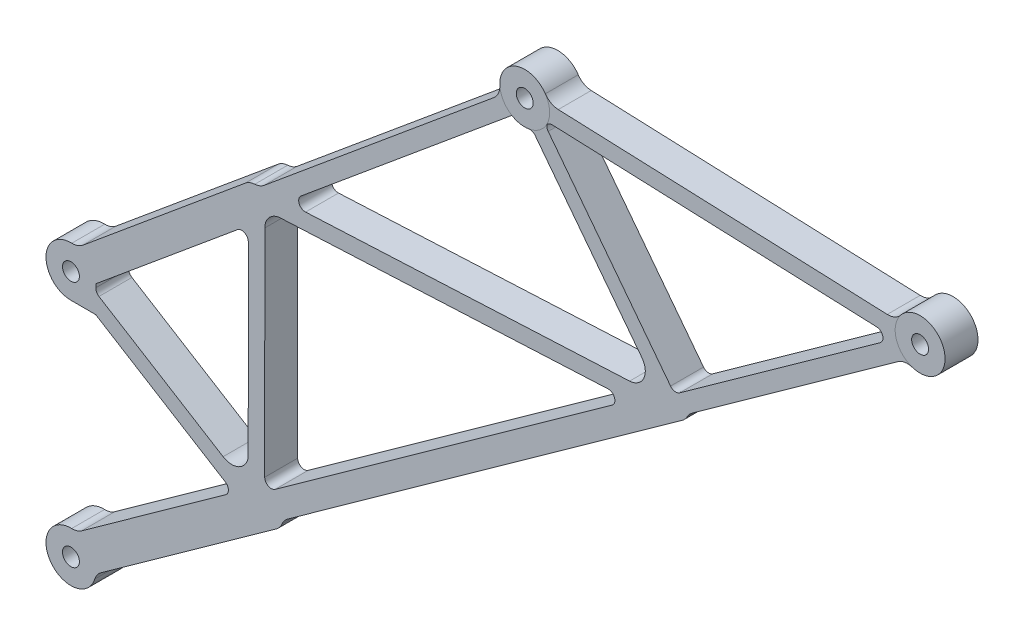
SolidWorks part; units mm, degrees
material "7075-T6 (SN)"
ref_plane "Front Plane" through (0, 0, 0) normal (0, 0, 1) x (1, 0, 0)
ref_plane "Top Plane" through (0, 0, 0) normal (0, 1, 0) x (1, 0, 0)
ref_plane "Right Plane" through (0, 0, 0) normal (1, 0, 0) x (0, 0, -1)
sketch "Sketch1" plane through (0, 0, 0) normal (0, 0, 1) x (1, 0, 0)
  line L0 (1800.568, -34.4734) -> (1473.2701, -269.0447) construction
  line L1 (1800.568, -34.4734) -> (1648.17, -28.4813) construction
  line L2 (1648.17, -28.4813) -> (1473.2701, -173.7947) construction
  line L3 (1547.9863, -115.8456) -> (1539.8135, -106.0088) construction
  line L4 (1473.2701, -269.0447) -> (1473.2701, -173.7947) construction
  line L7 (1806.1684, -42.2876) -> (1478.8705, -276.859)
  line L8 (1800.9457, -24.8669) -> (1648.5477, -18.8749)
  line L9 (1642.0262, -21.0867) -> (1467.1264, -166.4001)
  line L10 (1473.2701, -183.4086) -> (1482.7951, -183.4086)
  line L11 (1482.7951, -254.4058) -> (1482.7951, -183.4086) construction
  line L12 (1482.7951, -269.0447) -> (1482.7951, -173.7947) construction
  line L13 (1795.0417, -42.3402) -> (1709.5839, -103.5871)
  line L14 (1791.6252, -30.9443) -> (1657.3622, -25.6653)
  line L15 (1791.3758, -37.2894) -> (1657.1127, -32.0104)
  line L16 (1639.1612, -31.8383) -> (1543.9283, -110.9614)
  line L17 (1643.2192, -36.7225) -> (1541.6343, -121.1231)
  line L18 (1545.2991, -217.4222) -> (1541.6001, -212.2609) construction
  line L19 (1791.1982, -37.2824) -> (1705.8848, -98.4257)
  line L20 (1475.4382, -259.6785) -> (1536.0064, -216.2698)
  line L21 (1798.7185, -31.8927) -> (1471.4206, -266.4641) construction
  line L23 (1648.17, -28.4813) -> (1706.9348, -105.006) construction
  line L24 (1706.9348, -105.006) -> (1544.8124, -112.8199) construction
  line L25 (1544.8124, -112.8199) -> (1544.7729, -217.952) construction
  line L26 (1544.7729, -217.952) -> (1473.2701, -173.7947) construction
  line L29 (1651.1787, -37.6123) -> (1700.7207, -102.1268)
  line L30 (1656.2151, -33.7448) -> (1705.8848, -98.4257)
  line L31 (1650.6882, -26.5476) -> (1709.453, -103.0722) construction
  line L32 (1645.6518, -30.4151) -> (1704.4166, -106.9398) construction
  line L33 (1700.7207, -102.1268) -> (1556.1093, -109.0967)
  line L34 (1688.8733, -109.0552) -> (1547.9863, -115.8456)
  line L35 (1706.7819, -101.8347) -> (1544.6596, -109.6486) construction
  line L36 (1707.0876, -108.1773) -> (1544.9653, -115.9912) construction
  line L37 (1541.6343, -121.1231) -> (1541.6001, -212.2609)
  line L38 (1547.9863, -115.8456) -> (1547.9509, -210.053)
  line L39 (1541.6374, -112.8187) -> (1541.5979, -217.9508) construction
  line L40 (1547.9874, -112.8211) -> (1547.9479, -217.9531) construction
  line L41 (1541.6001, -212.2609) -> (1482.6593, -175.8614)
  line L42 (1536.0064, -216.2698) -> (1479.3227, -181.2642)
  line L43 (1543.1046, -220.6533) -> (1471.6019, -176.4961) construction
  line L44 (1546.4412, -215.2506) -> (1474.9384, -171.0933) construction
  line L47 (1554.2393, -218.8273) -> (1482.8363, -270.0011)
  line L48 (1650.199, -30.9234) -> (1475.2991, -176.2368) construction
  line L49 (1646.141, -26.0392) -> (1471.2411, -171.3526) construction
  line L50 (1800.4433, -37.6459) -> (1648.0453, -31.6539) construction
  line L51 (1800.6927, -31.3008) -> (1648.2947, -25.3088) construction
  line L54 (1802.4175, -37.054) -> (1475.1197, -271.6254) construction
  line L56 (1554.2393, -218.8273) -> (1553.1296, -217.2789)
  line L57 (1542.3863, -109.1054) -> (1475.7164, -164.4973)
  line L58 (1543.9283, -110.9614) -> (1542.3863, -109.1054)
  line L59 (1541.6331, -124.2612) -> (1482.8584, -173.0934)
  line L61 (1705.8848, -98.4257) -> (1713.3347, -108.8206) construction
  line L62 (1710.3237, -104.6193) -> (1553.1296, -217.2789)
  line L63 (1709.5839, -103.5871) -> (1710.3237, -104.6193)
  line L64 (1547.9509, -210.053) -> (1688.8733, -109.0552)
  circle A0 centre (1800.568, -34.4734) radius 3.2639 construction
  circle A1 centre (1648.17, -28.4813) radius 3.2639 construction
  circle A2 centre (1473.2701, -173.7947) radius 3.2639 construction
  circle A3 centre (1473.2701, -269.0447) radius 3.2639 construction
  circle A4 centre (1800.568, -34.4734) radius 3.2639
  circle A5 centre (1648.17, -28.4813) radius 3.2639
  circle A6 centre (1473.2701, -173.7947) radius 3.2639
  circle A7 centre (1473.2701, -269.0447) radius 3.2639
  circle A8 centre (1473.2701, -269.0447) radius 9.6139
  circle A9 centre (1473.2701, -173.7947) radius 9.6139
  circle A10 centre (1648.17, -28.4813) radius 9.6139
  circle A11 centre (1800.568, -34.4734) radius 9.6139
  dimension "D10" = 6.35
  dimension "D11" = 3.175
  dimension "D12" = 94.5014
  dimension "D26" = 6.35
  dimension "D27" = 5.588
  dimension "D28" = 5.588
  dimension "D29" = 4.445
  dimension "D30" = 4.445
  dimension "D13" = 114.3
  dimension "D1" = 6.35
  dimension "D3" = 9.525
  dimension "D4" = 3.175
  dimension "D5" = 3.175
  dimension "D6" = 3.175
  dimension "D7" = 3.175
  dimension "D8" = 3.175
  dimension "D9" = 3.175
  dimension "D15" = 3.175
  dimension "D16" = 3.175
  dimension "D17" = 3.175
  dimension "D18" = 3.175
  dimension "D19" = 3.175
  dimension "D22" = 3.175
  dimension "D23" = 3.175
extrude "Boss-Extrude1" add sketch "Sketch1" along normal mid plane 12.7 contours A8 A7 | A11 L15 L19 L30 A10 L29 L33 L17 L34 L64 L38 L37 L41 A9 L42 L20 A8 L47 L56 L62 L63 L13 | A9 A6 | A10 L16 L58 L57 A9 L59 L37 L17 | A10 A5 | A11 L14 A10 L15 | A11 A4 | L20 L42 region at (1800.6122, -43.8152, 0) region at (1464.1092, -270.8749, 0) region at (1749.9975, -69.7332, 0) region at (1724.369, -31.4773, 0) region at (1653.8712, -21.0807, 0) region at (1479.0973, -182.7389, 0) region at (1464.4838, -176.9685, 0) region at (1549.361, -110.5007, 0)
fillet "Fillet2" radius 6.35 10 edges at (1475.4382, -259.6785, 0) (1639.1612, -31.8383, 0) (1657.3622, -25.6653, 0) (1795.0417, -42.3402, 0) (1791.6252, -30.9443, 0) (1482.8363, -270.0011, 0) (1475.7164, -164.4973, 0) (1541.6001, -212.2609, 0) (1547.9863, -115.8456, 0) (1700.7207, -102.1268, 0)
fillet "Fillet3" radius 2.54 11 edges at (1791.1982, -37.2824, 0) (1482.6593, -175.8614, 0) (1536.0064, -216.2698, 0) (1556.1093, -109.0967, 0) (1705.8848, -98.4257, 0) (1651.1787, -37.6123, 0) (1657.1127, -32.0104, 0) (1656.2151, -33.7448, 0) (1541.6331, -124.2612, 0) (1547.9509, -210.053, 0) (1688.8733, -109.0552, 0)
sketch "Sketch3" plane through (0, 0, 6.35) normal (0, 0, 1) x (1, 0, 0)
  circle A0 centre (1648.17, -28.4813) radius 9.6139 construction
  circle A1 centre (1800.568, -34.4734) radius 9.6139 construction
  circle A2 centre (1648.17, -28.4813) radius 9.6139
  circle A3 centre (1800.568, -34.4734) radius 9.6139
split line "Split Line1"
fillet "Fillet6" radius 6.35 3 edges at (1543.9283, -110.9614, 0) (1709.5839, -103.5871, 0) (1553.1296, -217.2789, 0)
fillet "Fillet7" radius 6.35 3 edges at (1542.3863, -109.1054, 0) (1710.3237, -104.6193, 0) (1554.2393, -218.8273, 0)
